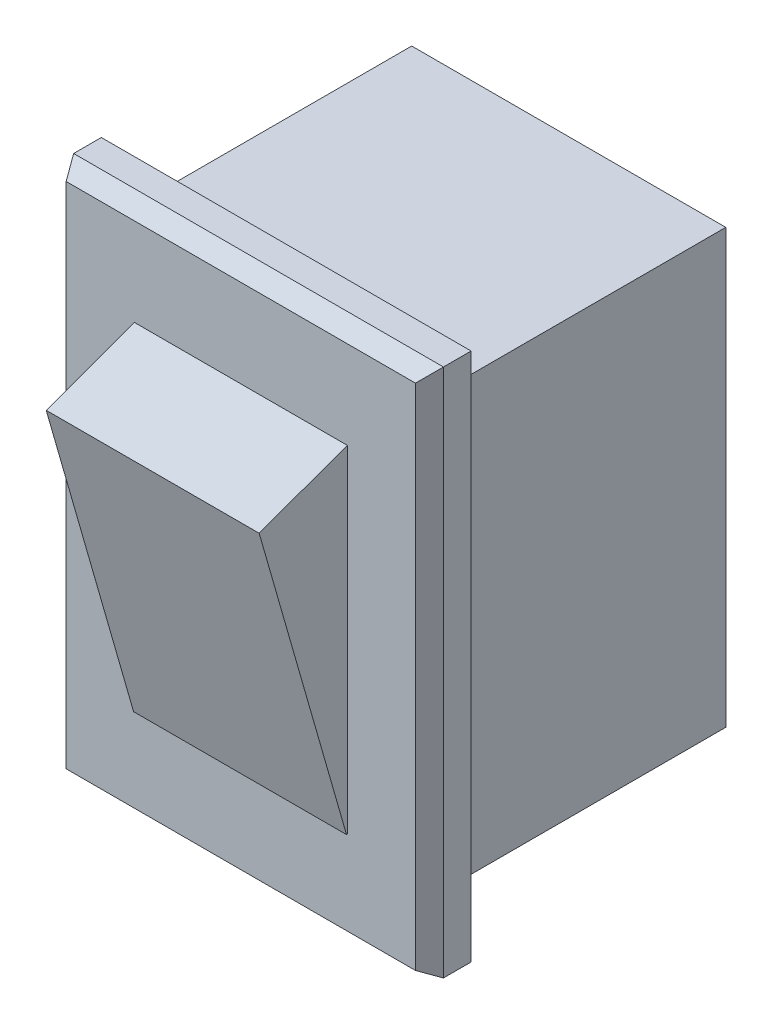
SolidWorks part; units mm, degrees
ref_plane "前视基准面" through (0, 0, 0) normal (0, 0, 1) x (1, 0, 0)
ref_plane "上视基准面" through (0, 0, 0) normal (0, 1, 0) x (1, 0, 0)
ref_plane "右视基准面" through (0, 0, 0) normal (1, 0, 0) x (0, 0, -1)
sketch "草图1" plane through (0, 0, 0) normal (0, 0, 1) x (1, 0, 0)
  line L1 (5.21, -7.455) -> (-5.21, -7.455)
  line L2 (5.21, -7.455) -> (5.21, 7.455)
  line L3 (5.21, 7.455) -> (-5.21, 7.455)
  line L4 (-5.21, -7.455) -> (-5.21, 7.455)
  line L5 (5.21, -7.455) -> (-5.21, 7.455) construction
  line L6 (5.21, 7.455) -> (-5.21, -7.455) construction
  point P0 (0, 0)
extrude "凸台-拉伸1" add sketch "草图1" along normal blind 1.28
ref_plane "基准面1" through (0, 0, 1.28) normal (0, 0, 1) x (1, 0, 0)
sketch "草图2" plane through (0, 0, 1.28) normal (0, 0, 1) x (1, 0, 0)
  line L2 (0, -4.8) -> (-3, -4.8)
  line L3 (0, -4.8) -> (3, -4.8)
  line L4 (3, -4.8) -> (3, 4.8)
  line L5 (3, 4.8) -> (-3, 4.8)
  line L6 (-3, 4.8) -> (-3, -4.8)
extrude "凸台-拉伸2" add sketch "草图2" along normal blind 3
chamfer "倒角3" distance 2 angle 80 1 edges at (0, -4.8, 4.28) first distance on face at (0, -4.8, 2.78)
chamfer "倒角4" distance 0.5 angle 30 4 edges at (0, 7.455, 1.28) (0, -7.455, 1.28) (5.21, 0, 1.28) (-5.21, 0, 1.28) first distance on face at (0, 7.455, 0.64) first distance on face at (0, -7.455, 0.64) first distance on face at (5.21, 0, 0.64) first distance on face at (-5.21, 0, 0.64)
chamfer "倒角5" distance 3 angle 20 1 edges at (0, 4.8, 3.9727) first distance on face at (0, 4.8, 2.6264)
chamfer "倒角6" distance 9 angle 6 1 edges at (0, -4.8, 2.28) first distance on face at (0, -0.513, 3.0359)
ref_plane "基准面2" through (0, 0, 0) normal (0, 0, -1) x (-1, 0, 0)
sketch "草图3" plane through (0, 0, 0) normal (0, 0, -1) x (-1, 0, 0)
  line L1 (4.425, -6.1) -> (-4.425, -6.1)
  line L2 (4.425, -6.1) -> (4.425, 6.1)
  line L3 (4.425, 6.1) -> (-4.425, 6.1)
  line L4 (-4.425, -6.1) -> (-4.425, 6.1)
  line L5 (4.425, -6.1) -> (-4.425, 6.1) construction
  line L6 (4.425, 6.1) -> (-4.425, -6.1) construction
  point P0 (0, 0)
  dimension "D1" = 8.85
  dimension "D2" = 12.2
extrude "凸台-拉伸3" add sketch "草图3" along normal blind 7.96
